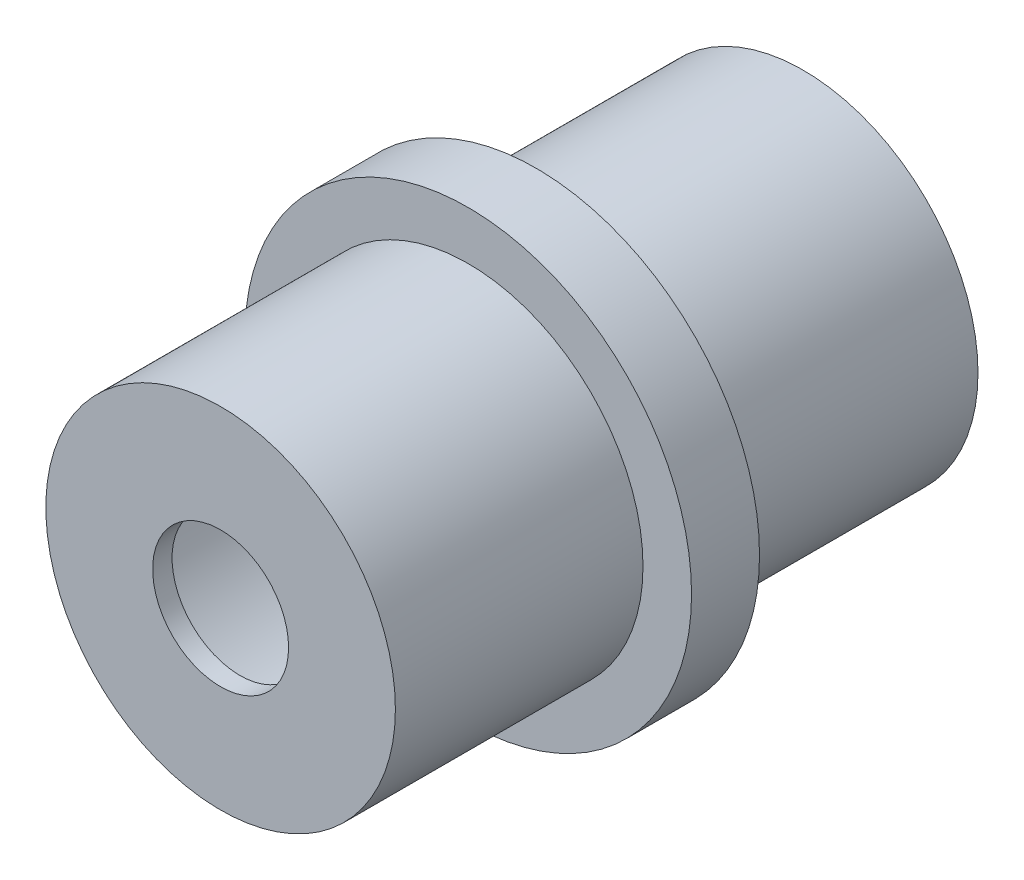
SolidWorks part; units mm, degrees
ref_plane "Front Plane" through (0, 0, 0) normal (0, 0, 1) x (1, 0, 0)
ref_plane "Top Plane" through (0, 0, 0) normal (0, 1, 0) x (1, 0, 0)
ref_plane "Right Plane" through (0, 0, 0) normal (1, 0, 0) x (0, 0, -1)
sketch "Sketch1" plane through (0, 0, 0) normal (1, 0, 0) x (0, 0, -1)
  line L0 (-60, 7) -> (-58, 7)
  line L1 (-60, 0) -> (0, 0)
  line L2 (-60, 0) -> (-60, 23)
  line L3 (-60, 23) -> (0, 23)
  line L4 (0, 0) -> (0, 23)
  line L5 (-1072.3815, 0) -> (1072.3815, 0) construction
  line L6 (-31, -974.342) -> (-31, 49025.6579)
  line L10 (-58, 0) -> (-2, 0)
  line L11 (-58, 0) -> (-58, 17)
  line L12 (-58, 17) -> (-2, 17)
  line L13 (-2, 0) -> (-2, 17)
  line L15 (-60, 18) -> (0, 18)
  line L16 (-27.5, 23) -> (-27.5, 18)
  line L17 (-2, 13) -> (0, 13)
  line L18 (-34.5, 23) -> (-34.5, 18)
  point P14 (-31, 17)
  dimension "D3" = 56
  dimension "D1" = 2
  dimension "D2" = 17
  dimension "D6" = 27
  dimension "D5" = 7
  dimension "D9" = 4
  dimension "D4" = 6
  dimension "D7" = 2
  dimension "D8" = 1
  dimension "D10" = 7
revolve "Revolve1" add sketch "Sketch1" angle 360 about L5 region at (0, 12.5, 59.6898) region at (0, 20.5, 32.75) region at (0, 17.5, 30.686) region at (0, 20.5, 29.25)
ref_axis "Axis1" through (0, 0, -68.4732) along (0, 0, 1)
ref_axis "Axis2" through (0, -974.342, 31) along (0, 1, 0)
ref_plane "Plane1" through (0, 0, 31) normal (0, 0, 1) x (1, 0, 0)
sketch "Sketch3" plane through (0, 0, 31) normal (0, 0, 1) x (1, 0, 0)
  line L0 (0, -999.5695) -> (0, 49000.4305) construction
  line L1 (-340.1578, -934.5758) -> (16760.8494, 46050.0552) construction
  line L2 (-1, 19.9725) -> (1, 19.9725)
  line L3 (338.8634, -931.0195) -> (-16762.1438, 46053.6116) construction
  line L4 (1, 19.9725) -> (4.5052, 16.5181) construction
  line L5 (0, 19.9725) -> (0, 23.1006) construction
  line L6 (2.0302, 19.9725) -> (-0.0328, 19.9725) construction
  line L7 (3.5107, 17.4982) -> (0.2868, 20.6753) construction
  line L8 (1, 19.9725) -> (1.1001, 21.9725) construction
  line L9 (4.5052, 16.5181) -> (4.684, 16.342)
  line L10 (6.4984, 17.8542) -> (7.5244, 20.6732)
  line L11 (-6.4984, 17.8542) -> (-7.5244, 20.6732)
  line L12 (-4.5052, 16.5181) -> (-4.684, 16.342)
  circle A4 centre (0, 0) radius 17 construction
  circle A6 centre (0, 0) radius 17
  circle A8 centre (5.2072, 17.2304) radius 1 construction
  arc A10 (6.4984, 17.8542) -> (-6.4984, 17.8542) centre (0, 0) cw
  circle A13 centre (0, 0) radius 22
  spline S0 degree 3 poles (1, 19.9725) (1.8375, 19.9725) (3.4007, 17.6066) (4.5052, 16.5181) knots 0 0 0 0 1 1 1 1
  spline S1 degree 3 poles (-1, 19.9725) (-1.8375, 19.9725) (-3.4007, 17.6066) (-4.5052, 16.5181) knots 0 0 0 0 1 1 1 1
  point P11 (0, 19.9725)
  point P13 (5.8143, 15.9748)
  point P16 (0, 22)
  point P20 (0, 19.9725)
  dimension "D2" = 2
  dimension "D4" = 20
  dimension "D1" = 5
  dimension "D3" = 1
  dimension "D5" = 2
  dimension "D6" = 2
extrude "Cut-Extrude1" cut sketch "Sketch3" against normal mid plane 4 contours L10 A13 L11 A10 S1 L2 S0 L9 A6 L12 region at (0, -18.441, 31)
extrude "Cut-Extrude2" cut sketch "Sketch3<5>" against normal mid plane 2 contours A6 | L2 S1 L12 A6 L9 S0 | L11 A13 L10 A10 region at (0, 18.1135, 31) region at (0, 0, 31) region at (7.5874, 19.0541, 31)
sketch "Sketch3<5>" plane through (0, 0, 31) normal (0, 0, 1) x (1, 0, 0) same geometry as "Sketch3"
ref_plane "Plane2" through (-7.5244, 20.6732, 32) normal (-0.9397, -0.342, 0) x (0, 0, 1)
equation "\"key_pin_length\"= 25.00mm"
equation "\"key_pin_dia\"= 20.00mm"
equation "\"driver_pin_travel\"= 3.00mm"
equation "\"driver_pin_dia\"= 0.3mm"
equation "\"plug_wall_thickness\" = 2mm"
equation "\"plug_spring_solid_length\"= 2mm"
equation "\"plug_length\"= 2 * \"key_pin_length\" + 2 * \"plug_wall_thickness\" + \"plug_spring_solid_length\""
equation "\"D3@Sketch1\"= \"plug_length\""
equation "\"D6@Sketch1\"= \"plug_wall_thickness\" + \"key_pin_length\""
equation "\"D7@Sketch1\"= \"D1@Sketch1\""
equation "\"driver_pin_head_dia\" = 2mm"
equation "\"D1@Sketch3\"=\"driver_pin_head_dia\"+\"driver_pin_travel\""
equation "\"true_gate_depth\" = 1.25mm"
equation "\"D4@Sketch1\"= \"driver_pin_head_dia\" + \"driver_pin_travel\" + 1mm"
equation "\"driver_pin_neck_dia\"= 2.00mm"
equation "\"driver_pin_head_length\" = 2mm"
equation "\"D1@Cut-Extrude1\"= \"driver_pin_neck_dia\" + \"driver_pin_head_length\""
equation "\"D1@Cut-Extrude2\"=\"driver_pin_neck_dia\""
equation "\"plug_dia\"= \"key_pin_dia\" + 2*(\"driver_pin_travel\" + 1mm + \"plug_spring_solid_length\" + 1mm)"
equation "\"D2@Sketch1\"=\"plug_dia\"/2"
equation "\"D2@Sketch3\"=\"driver_pin_head_dia\""
equation "\"D5@Sketch3\"=\"driver_pin_head_dia\""
equation "\"D6@Sketch3\"=\"driver_pin_head_dia\""
